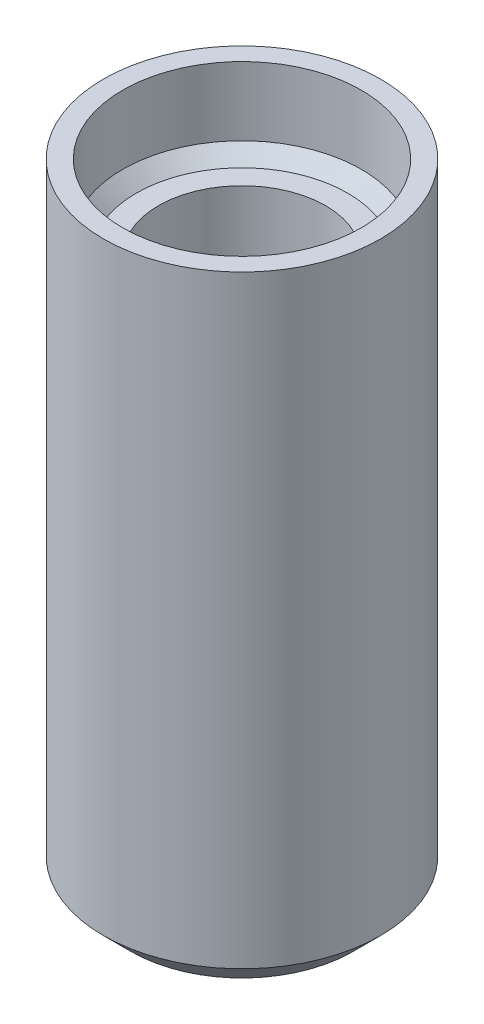
SolidWorks part; units mm, degrees
ref_plane "Front Plane" through (0, 0, 0) normal (0, 0, 1) x (1, 0, 0)
ref_plane "Top Plane" through (0, 0, 0) normal (0, 1, 0) x (1, 0, 0)
ref_plane "Right Plane" through (0, 0, 0) normal (1, 0, 0) x (0, 0, -1)
sketch "Sketch1" plane through (0, 0, 0) normal (0, 1, 0) x (1, 0, 0)
  line L0 (-2.5652, -1.65) -> (2.5652, -1.65)
  circle A0 centre (0, 0) radius 3.05
  circle A1 centre (0, 0) radius 5.05
  dimension "D1" = 6.1
  dimension "D3" = 1.65
  dimension "D2" = 2
extrude "Boss-Extrude1" add sketch "Sketch1" along normal blind 20 contours A1 A0 | L0 A0 region at (0, 0, 2.2227) region at (-4.9072, 0, 0)
sketch "Sketch2" plane through (0, 0, 0) normal (0, -1, 0) x (1, 0, 0)
  circle A1 centre (0, 0) radius 5.05
  circle A2 centre (0, 0) radius 5.05
  dimension "D1" = 0
extrude "Boss-Extrude2" add sketch "Sketch2" against normal blind 2
sketch "Sketch4" plane through (0, 20, 0) normal (0, 1, 0) x (1, 0, 0)
  circle A0 centre (0, 0) radius 4.35
  circle A1 centre (0, 0) radius 5.05
  circle A2 centre (0, 0) radius 5.05
  dimension "D1" = 0
  dimension "D2" = 0.7
extrude "Boss-Extrude3" add sketch "Sketch4" along normal blind 3
chamfer "Chamfer1" distance 1 angle 45 1 edges at (0, 0, 5.05)
chamfer "Chamfer2" distance 0.5 angle 45 1 edges at (0, 20, 4.35)
equation "\"ID\"= 6.3"
equation "\"notch\"= 6.3 / 2 - 1.5"
equation "\"D3@Sketch1\"=\"notch\""
